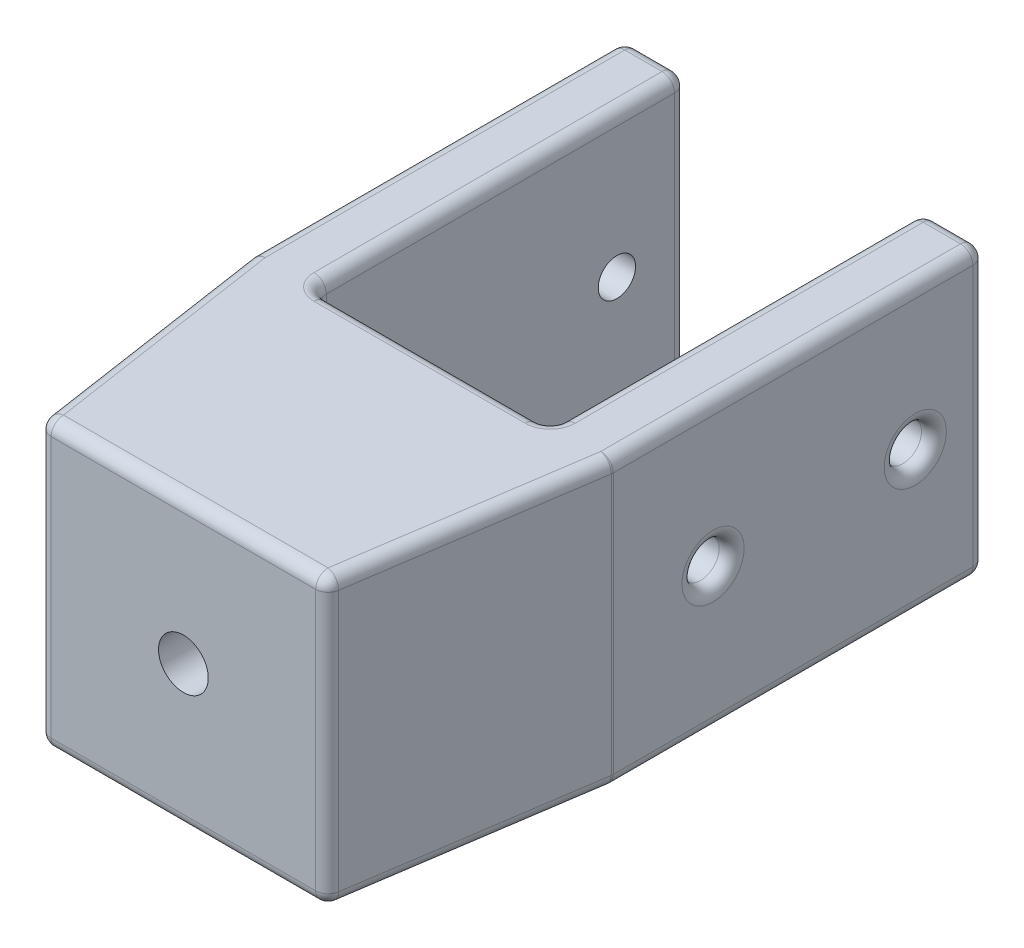
SolidWorks part; units mm, degrees
ref_plane "Front Plane" through (0, 0, 0) normal (0, 0, 1) x (1, 0, 0)
ref_plane "Top Plane" through (0, 0, 0) normal (0, 1, 0) x (1, 0, 0)
ref_plane "Right Plane" through (0, 0, 0) normal (1, 0, 0) x (0, 0, -1)
sketch "Sketch2" plane through (0, 0, 0) normal (0, 0, 1) x (1, 0, 0)
  line L5 (-11.5, -11.5) -> (11.5, -11.5)
  line L6 (-11.5, -11.5) -> (-11.5, 11.5)
  line L7 (-11.5, 11.5) -> (11.5, 11.5)
  line L8 (11.5, -11.5) -> (11.5, 11.5)
  line L9 (-11.5, -11.5) -> (11.5, 11.5) construction
  line L10 (-11.5, 11.5) -> (11.5, -11.5) construction
  dimension "D2" = 23
extrude "Boss-Extrude1" add sketch "Sketch2" along normal blind 5 contours L5 L8 L7 L6 region at (0, 0, 0)
extrude "Boss-Extrude2" add sketch "Sketch2<3>" against normal blind 45 contours L7 L6 | L8 L7 | L5 L8 | L6 L5 region at (0, 0, 0)
sketch "Sketch2<3>" plane through (0, 0, 0) normal (0, 0, 1) x (1, 0, 0) same geometry as "Sketch2"
sketch "Sketch4" plane through (0, 11.5, 0) normal (0, 1, 0) x (1, 0, 0)
  line L1 (-6.5, 10) -> (6.5, 10)
  line L2 (-6.5, 10) -> (-6.5, 0)
  line L3 (-6.5, 0) -> (6.5, 0)
  line L4 (6.5, 10) -> (6.5, 0)
  line L5 (-6.5, 10) -> (6.5, 0) construction
  line L6 (-6.5, 0) -> (6.5, 10) construction
  line L7 (11.5, 45) -> (11.5, -5) construction
  line L8 (-14.5, 15) -> (-11.5, -5)
  line L9 (-9.5, 15) -> (9.5, 15)
  line L10 (-9.5, 15) -> (-9.5, 45)
  line L11 (-9.5, 45) -> (9.5, 45)
  line L12 (9.5, 15) -> (9.5, 45)
  line L13 (-9.5, 15) -> (9.5, 45) construction
  line L14 (-9.5, 45) -> (9.5, 15) construction
  line L15 (0, 45) -> (0, 15) construction
  line L16 (14.5, 15) -> (11.5, -5)
  line L17 (-14.5, 15) -> (-9.5, 15)
  line L18 (-14.5, 15) -> (-14.5, 45)
  line L19 (-14.5, 45) -> (-9.5, 45)
  line L20 (-9.5, 15) -> (-9.5, 45)
  line L21 (-14.5, 15) -> (-9.5, 45) construction
  line L22 (-14.5, 45) -> (-9.5, 15) construction
  line L23 (14.5, 45) -> (9.5, 15) construction
  line L24 (14.5, 15) -> (9.5, 45) construction
  line L25 (9.5, 15) -> (9.5, 45)
  line L26 (14.5, 45) -> (9.5, 45)
  line L27 (14.5, 15) -> (14.5, 45)
  line L28 (14.5, 15) -> (9.5, 15)
  line L29 (9.5, 15) -> (9.5, 45)
  line L35 (-11.5, -5) -> (11.5, -5) construction
  line L36 (11.5, -5) -> (11.5, 45) construction
  point P0 (0, 5)
  point P5 (0, 0)
  point P6 (0, 0)
  point P11 (0, 30)
  point P18 (0, 0)
  point P19 (-12, 30)
  point P20 (0, 30)
  point P27 (12, 30)
  point P35 (0, 0)
  line M11 (11.5, -5) -> (11.5, 45)
  line M12 (11.5, 45) -> (-11.5, 45)
  line M13 (-11.5, 45) -> (-11.5, -5)
  dimension "D1" = 5
  dimension "D2" = 10
  dimension "D3" = 19
  dimension "D4" = 30
  dimension "D5" = 5
  dimension "D6" = 5
  dimension "D7" = 5
extrude "Boss-Extrude3" add sketch "Sketch4" against normal up to surface (23 mm away) contours L28 L27 L26 M11 | L28 M11 | L19 L18 L17 M13 | L17 M13 region at (-12.5, 11.5, -8.3333) region at (-13, 11.5, -30) region at (13, 11.5, -30) region at (12.5, 11.5, -8.3333) up to face at (0, -11.5, -20)
extrude "Cut-Extrude1" cut sketch "Sketch4<4>" against normal blind 50 contours L9 L12 L10 M12 region at (0, 11.5, -30)
sketch "Sketch4<4>" plane through (0, 11.5, 0) normal (0, 1, 0) x (1, 0, 0) same geometry as "Sketch4"
sketch "Sketch6" plane through (0, 0, -15) normal (0, 0, -1) x (-1, 0, 0)
  circle A0 centre (0, 0) radius 2
  circle A1 centre (0, 0) radius 4
  dimension "D1" = 8
  dimension "D2" = 4
extrude "Cut-Extrude3" cut sketch "Sketch6" against normal blind 15
extrude "Cut-Extrude4" cut sketch "Sketch6<2>" against normal through all contours A0 region at (0, 0, -15)
sketch "Sketch6<2>" plane through (0, 0, -15) normal (0, 0, -1) x (-1, 0, 0) same geometry as "Sketch6"
sketch "Sketch7" plane through (-14.5, 0, 0) normal (-1, 0, 0) x (0, 0, 1)
  circle A0 centre (-39.367, 0) radius 1.5
  circle A1 centre (-23.0987, 0) radius 1.5
  point P4 (0, 0)
  point P6 (0, 0)
  dimension "D1" = 3
extrude "Cut-Extrude5" cut sketch "Sketch7" against normal through all
fillet "Fillet2" radius 1 30 edges at (-13, 11.5, -5) (-11.5, 0, 5) (0, 11.5, 5) (11.5, 0, 5) (13, 11.5, -5) (14.5, 0, -15) (14.5, 11.5, -30) (14.5, 0, -45) (12, 11.5, -45) (0, 11.5, -15) (-14.5, 11.5, -30) (-12, 11.5, -45) (-14.5, 0, -45) (-14.5, -11.5, -30) (-12, -11.5, -45) (-9.5, -11.5, -30) (-9.5, 0, -45) (-9.5, 11.5, -30) (-9.5, 0, -15) (0, -11.5, -15) (9.5, -11.5, -30) (9.5, 0, -15) (9.5, 11.5, -30) (9.5, 0, -45) (12, -11.5, -45) (14.5, -11.5, -30) (13, -11.5, -5) (0, -11.5, 5) (-13, -11.5, -5) (-14.5, 0, -15)
fillet "Fillet3" radius 1 6 edges at (-2, 0, 0) (14.5, 0, -37.867) (-14.5, 0, -21.5987) (-14.5, 0, -37.867) (14.5, 0, -21.5987) (-4, 0, -15)
